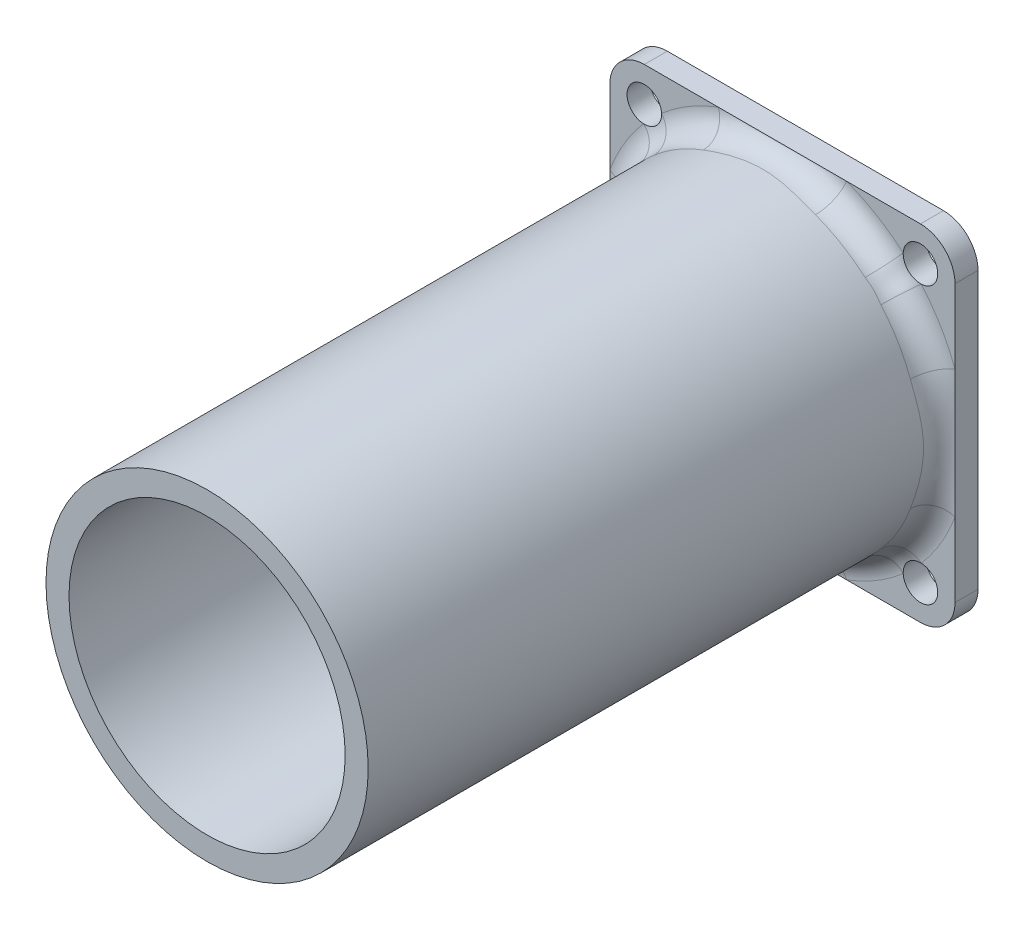
SolidWorks part; units mm, degrees
ref_plane "Plan de face" through (0, 0, 0) normal (0, 0, 1) x (1, 0, 0)
ref_plane "Plan de dessus" through (0, 0, 0) normal (0, 1, 0) x (1, 0, 0)
ref_plane "Plan de droite" through (0, 0, 0) normal (1, 0, 0) x (0, 0, -1)
sketch "Esquisse1" plane through (0, 0, 0) normal (0, 0, 1) x (1, 0, 0)
  line L1 (-15, -15) -> (15, -15)
  line L2 (-15, -15) -> (-15, 15)
  line L3 (-15, 15) -> (15, 15)
  line L4 (15, -15) -> (15, 15)
  line L5 (-15, -15) -> (15, 15) construction
  line L6 (-15, 15) -> (15, -15) construction
  circle A0 centre (0, 0) radius 12
  circle A1 centre (-12, 12) radius 1.5
  circle A2 centre (12, 12) radius 1.5
  circle A3 centre (12, -12) radius 1.5
  circle A4 centre (-12, -12) radius 1.5
  point P0 (0, 0)
  point P19 (0, 0)
  dimension "D2" = 24
  dimension "D3" = 3
  dimension "D1" = 30
  dimension "D4" = 3
  dimension "D5" = 4
extrude "Boss.-Extru.1" add sketch "Esquisse1" along normal blind 2
sketch "Esquisse3" plane through (0, 0, 2) normal (0, 0, 1) x (1, 0, 0)
  circle A0 centre (0, 0) radius 12 construction
  circle A1 centre (0, 0) radius 12
  circle A2 centre (0, 0) radius 14
  dimension "D1" = 28
extrude "Boss.-Extru.2" add sketch "Esquisse3" along normal blind 50
fillet "Congé1" radius 3 4 edges at (-15, -15, 1) (15, -15, 1) (15, 15, 1) (-15, 15, 1)
fillet "Congé2" radius 2 1 edges at (14, 0, 2)
